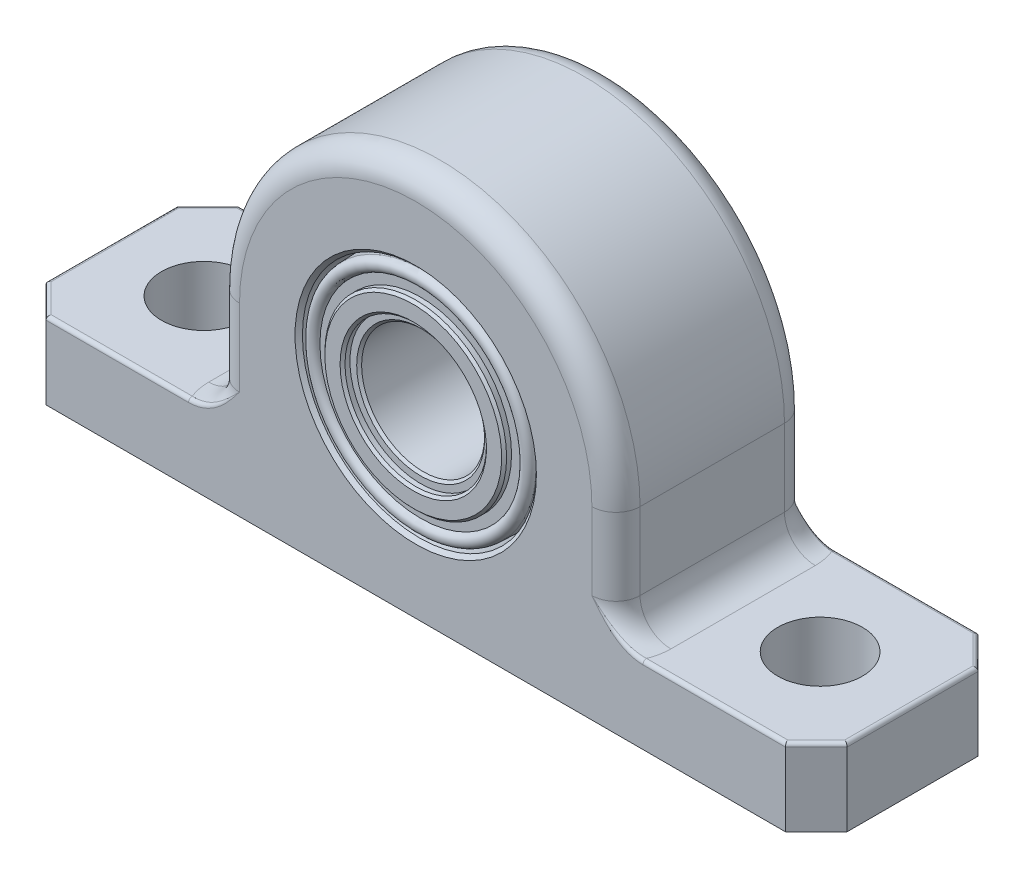
SolidWorks part; units mm, degrees
ref_plane "Front Plane" through (0, 0, 0) normal (0, 0, 1) x (1, 0, 0)
ref_plane "Top Plane" through (0, 0, 0) normal (0, 1, 0) x (1, 0, 0)
ref_plane "Right Plane" through (0, 0, 0) normal (1, 0, 0) x (0, 0, -1)
sketch "Sketch1" plane through (0, 0, 0) normal (0, 0, 1) x (1, 0, 0)
  line L0 (-41.275, 0) -> (41.275, 0)
  line L1 (41.275, 0) -> (41.275, 7.9375)
  line L2 (-41.275, 0) -> (-41.275, 7.9375)
  line L3 (-41.275, 7.9375) -> (-20.6375, 7.9375)
  line L4 (41.275, 7.9375) -> (20.6375, 7.9375)
  line L5 (-20.6375, 7.9375) -> (-20.6375, 19.05)
  line L6 (20.6375, 7.9375) -> (20.6375, 19.05)
  line L7 (0, 0) -> (0, 39.6875) construction
  line L8 (4.4811, 23.5311) -> (14.5929, 33.6429) construction
  circle A0 centre (0, 19.05) radius 6.3373
  arc A1 (20.6375, 19.05) -> (-20.6375, 19.05) centre (0, 19.05) ccw
  circle A2 centre (0, 19.05) radius 12.0574 construction
  point P16 (8.5259, 27.5759)
  point P17 (0, 25.3873)
  point P18 (0, 31.1074)
  dimension "ID" = 12.6746
  dimension "Overall Height" = 39.6875
  dimension "Overall Length" = 82.55
  dimension "CAD B" = 7.9375
  dimension "Center Height" = 19.05
  dimension "D1" = 45
  dimension "D2" = 14.3002
  dimension "D3" = 5.7201
sketch "Sketch2" plane through (0, 0, 0) normal (0, 1, 0) x (1, 0, 0)
  line L0 (-31.75, 0) -> (31.75, 0) construction
  line L1 (-41.275, -9.9219) -> (41.275, 9.9219) construction
  line L2 (-41.275, 9.9219) -> (41.275, 9.9219)
  line L3 (-41.275, 9.9219) -> (-41.275, -9.9219)
  line L4 (-41.275, -9.9219) -> (41.275, -9.9219)
  line L5 (41.275, 9.9219) -> (41.275, -9.9219)
  circle A0 centre (-31.75, 0) radius 4.3656
  circle A1 centre (31.75, 0) radius 4.3656
  dimension "Mounting Hole" = 8.7312
  dimension "Mounting Center" = 63.5
  dimension "Overall Width" = 19.8438
sketch "Sketch3" plane through (0, 0, 0) normal (0, 0, 1) x (1, 0, 0)
  line L0 (-41.275, 0) -> (-41.275, 7.9375) construction
  line L1 (-41.275, 0) -> (41.275, 0) construction
  line L2 (-41.275, 7.9375) -> (-20.6375, 7.9375) construction
  line L3 (41.275, 7.9375) -> (20.6375, 7.9375) construction
  line L4 (41.275, 0) -> (41.275, 7.9375) construction
  line L5 (20.6375, 7.9375) -> (20.6375, 19.05) construction
  line L6 (-20.6375, 7.9375) -> (-20.6375, 19.05) construction
  line L7 (-41.275, 0) -> (-41.275, 7.9375)
  line L8 (-41.275, 0) -> (41.275, 0)
  line L9 (-41.275, 7.9375) -> (-20.6375, 7.9375)
  line L10 (41.275, 7.9375) -> (20.6375, 7.9375)
  line L11 (41.275, 0) -> (41.275, 7.9375)
  line L12 (20.6375, 7.9375) -> (20.6375, 19.05)
  line L13 (-20.6375, 7.9375) -> (-20.6375, 19.05)
  arc A0 (20.6375, 19.05) -> (-20.6375, 19.05) centre (0, 19.05) ccw construction
  circle A1 centre (0, 19.05) radius 12.0574 construction
  arc A2 (20.6375, 19.05) -> (-20.6375, 19.05) centre (0, 19.05) ccw
  circle A3 centre (0, 19.05) radius 12.0574
extrude "Boss-Extrude1" add sketch "Sketch3" against normal up to vertex (9.9219 mm away) and the other way up to vertex (9.9219 mm away) up to point (-41.275, 0, -9.9219) other way up to point (-41.275, 0, 9.9219)
sketch "Sketch4" plane through (0, 0, 0) normal (0, 1, 0) x (1, 0, 0)
  circle A0 centre (-31.75, 0) radius 4.3656 construction
  circle A1 centre (31.75, 0) radius 4.3656 construction
  circle A2 centre (-31.75, 0) radius 4.3656
  circle A3 centre (31.75, 0) radius 4.3656
extrude "Cut-Extrude1" cut sketch "Sketch4" along normal through all
chamfer "Chamfer1" distance 3.175 angle 45 4 edges at (-41.275, 3.9688, -9.9219) (41.275, 3.9688, 9.9219) (41.275, 3.9688, -9.9219) (-41.275, 3.9688, 9.9219)
fillet "Fillet1" radius 2.4805 6 edges at (-20.6375, 13.4938, -9.9219) (0, 39.6875, -9.9219) (-20.6375, 13.4938, 9.9219) (0, 39.6875, 9.9219) (20.6375, 13.4938, -9.9219) (20.6375, 13.4938, 9.9219)
fillet "Fillet2" radius 3.175 6 edges at (-19.911, 7.9375, -9.1954) (-19.911, 7.9375, 9.1954) (19.911, 7.9375, -9.1954) (19.911, 7.9375, 9.1954) (-20.6375, 7.9375, 0) (20.6375, 7.9375, 0)
chamfer "Chamfer2" distance 0.381 angle 45 2 edges at (12.0574, 19.05, 9.9219) (12.0574, 19.05, -9.9219)
fillet "Fillet3" radius 0.381 14 edges at (-21.8256, 8.1842, -9.9219) (-21.8256, 8.1842, 9.9219) (21.8256, 8.1842, -9.9219) (21.8256, 8.1842, 9.9219) (-30.6698, 7.9375, -9.9219) (-39.6875, 7.9375, -8.3344) (-41.275, 7.9375, 0) (-39.6875, 7.9375, 8.3344) (-30.6698, 7.9375, 9.9219) (30.6698, 7.9375, -9.9219) (39.6875, 7.9375, -8.3344) (41.275, 7.9375, 0) (39.6875, 7.9375, 8.3344) (30.6698, 7.9375, 9.9219)
sketch "Sketch5" plane through (0, 0, 0) normal (1, 0, 0) x (0, 0, -1)
  line L1 (-9.9219, 31.1074) -> (9.9219, 31.1074)
  line L2 (-9.9219, 31.1074) -> (-9.9219, 25.3873)
  line L3 (-9.9219, 25.3873) -> (9.9219, 25.3873)
  line L4 (9.9219, 31.1074) -> (9.9219, 25.3873)
sketch "Sketch6" plane through (0, 0, 0) normal (1, 0, 0) x (0, 0, -1)
  line L0 (0, 31.1074) -> (9.9219, 31.1074)
  line L1 (-9.9219, 31.1074) -> (9.9219, 31.1074) construction
  line L2 (0, 31.1074) -> (-9.2577, 30.7841)
  line L3 (-9.9219, 31.1074) -> (-9.9219, 25.3873) construction
  line L4 (-9.4139, 29.4321) -> (-9.4139, 28.4179)
  line L5 (-9.4139, 28.4179) -> (-10.1759, 28.4179)
  line L6 (-10.1759, 28.4179) -> (-10.1759, 26.3379)
  line L7 (-10.1759, 26.3379) -> (-9.4139, 26.3379)
  line L8 (-9.4139, 26.3379) -> (-9.4139, 25.3873)
  line L9 (-9.9219, 25.3873) -> (9.9219, 25.3873) construction
  line L10 (-9.4139, 25.3873) -> (7.8899, 25.3873)
  line L11 (9.9219, 31.1074) -> (9.9219, 29.4321)
  line L12 (9.9219, 31.1074) -> (9.9219, 25.3873) construction
  line L13 (9.9219, 29.4321) -> (6.1119, 29.4321)
  line L14 (6.1119, 29.4321) -> (6.1119, 28.4179)
  line L15 (6.1119, 28.4179) -> (8.6519, 28.4179)
  line L16 (8.6519, 28.4179) -> (8.6519, 26.3379)
  line L17 (8.6519, 26.3379) -> (7.8899, 26.3379)
  line L18 (7.8899, 26.3379) -> (7.8899, 25.3873)
  line L20 (-9.9219, 19.05) -> (9.9219, 19.05) construction
  line L21 (-9.9219, 0) -> (-9.9219, 7.5565) construction
  arc A0 (-9.2577, 30.7841) -> (-9.4139, 29.4321) centre (-9.2336, 30.0963) ccw
  dimension "D1" = 2
  dimension "D2" = 0.254
  dimension "D3" = 0.762
  dimension "D4" = 5.7201
  dimension "D5" = 1.27
  dimension "D6" = 2.54
  dimension "D7" = 2.08
  dimension "D8" = 1.352
  dimension "D9" = 14.5758
revolve "Revolve1" add sketch "Sketch6" angle 360 about L20
chamfer "Chamfer3" distance 0.254 angle 45 6 edges at (7.2879, 19.05, -8.6519) (9.3679, 19.05, -8.6519) (6.3373, 19.05, 9.4139) (6.3373, 19.05, -7.8899) (9.3679, 19.05, 10.1759) (7.2879, 19.05, 10.1759)
equation "\"D3@Sketch1\"=\"D2@Sketch1\"/2.50"
equation "\"D1@Fillet1\"=\"Overall Width@Sketch2\"/8"
equation "\"D7@Sketch6\"=\"D4@Sketch6\"/2.750"
equation "\"D8@Sketch6\"=\"D7@Sketch6\"*.65"
equation "\"D9@Sketch6\"=\"ID@Sketch1\"*1.15"
